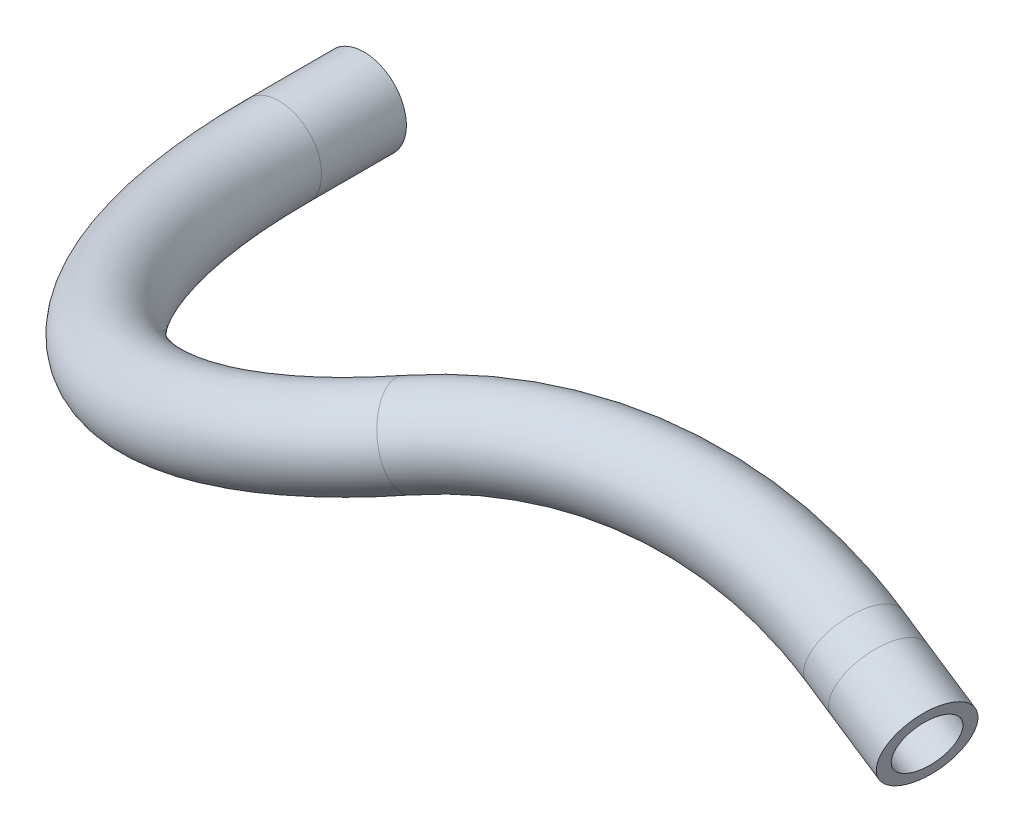
SolidWorks part; units mm, degrees
material "Silicon Rubber"
ref_plane "X-Y Datum" through (0, 0, 0) normal (0, 0, 1) x (1, 0, 0)
ref_plane "X-Z Datum" through (0, 0, 0) normal (0, 1, 0) x (1, 0, 0)
ref_plane "Y-Z Datum" through (0, 0, 0) normal (1, 0, 0) x (0, 0, -1)
sketch3d "3DSketch1"
  line L0 (23.5, 73, -27) -> (23.5, 73, 0)
  line L1 (323.6965, 131.8098, 109.239) -> (313.8469, 135.1512, 107.3062)
  line L2 (323.6965, 131.8098, 109.239) -> (342.6155, 125.3915, 112.9515)
  circle A0 centre (23.5, 73, 0) radius 8 construction
  circle A1 centre (23.5, 73, 0) radius 8 construction
  circle A2 centre (23.5, 73, -27) radius 10 construction
  circle A3 centre (23.5, 73, -27) radius 10 construction
  circle A4 centre (313.8469, 135.1512, 107.3062) radius 8.2804 construction
  circle A5 centre (313.8469, 135.1512, 107.3062) radius 8.2804 construction
  circle A6 centre (323.6965, 131.8098, 109.239) radius 8.2804 construction
  circle A7 centre (323.6965, 131.8098, 109.239) radius 8.2804 construction
  arc A11 (23.5, 73, 0) -> (183.3088, 133.854, 119.1332) centre (142.1863, 118.1948, 0) ccw
  arc A12 (313.8469, 135.1512, 107.3062) -> (183.3088, 133.854, 119.1332) centre (257.7569, 24.8827, 202.5082) ccw
  point P2 (23.5, 73, -8)
  point P4 (23.5, 73, -8)
  point P7 (23.5, 73, -17)
  point P9 (23.5, 73, -17)
  point P12 (321.5563, 132.5358, 108.819)
  point P14 (321.5563, 132.5358, 108.819)
  point P17 (331.406, 129.1943, 110.7518)
  point P19 (331.406, 129.1943, 110.7518)
  point P25 (96.9914, 236.8811, 0)
  point P30 (267.6811, 123.7682, 322.8902)
  dimension "D1" = 127
  dimension "D2" = 20.32
sweep "Sweep1" add path "3DSketch1" circular profile diameter 26.9875 parameters "D3"=26.9875
sweep "Cut-Sweep1" cut path "3DSketch1<2>" circular profile diameter 19.05 parameters "D3"=19.05
sketch3d "3DSketch1<2>" same geometry as "3DSketch1"
